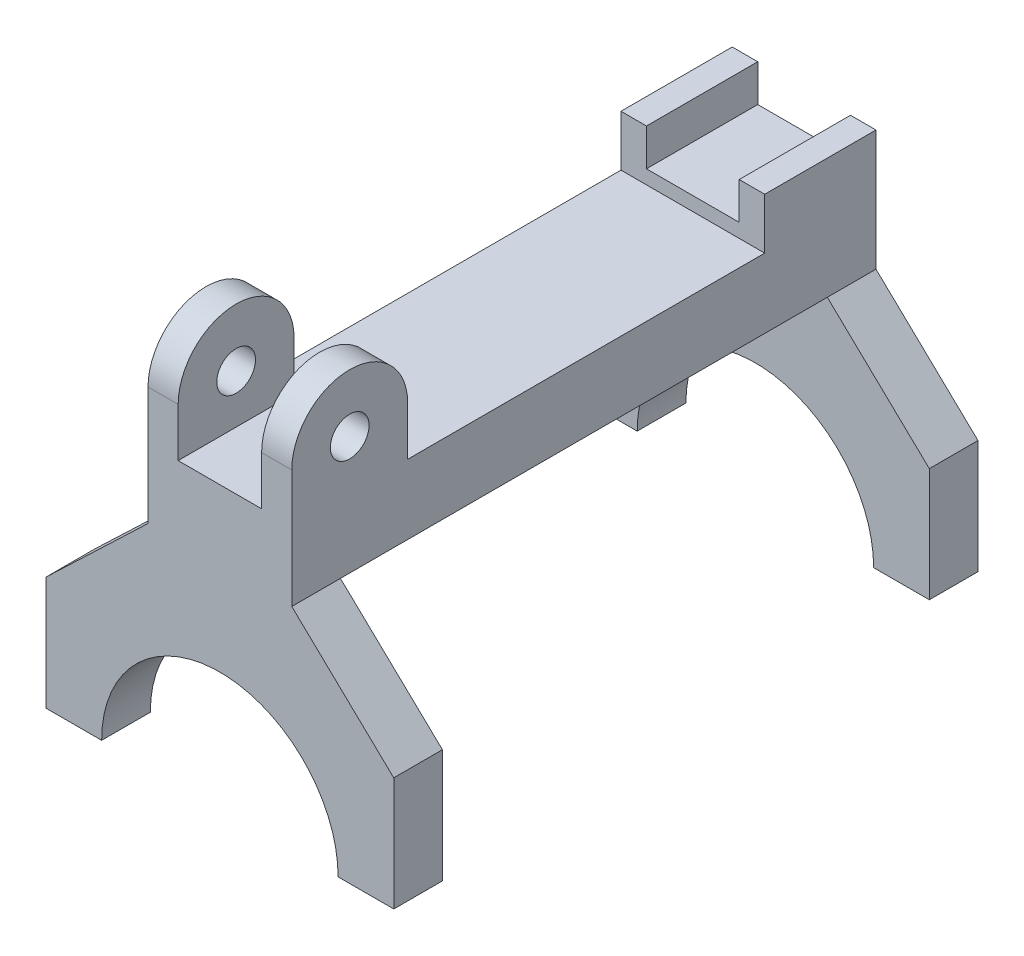
SolidWorks part; units mm, degrees
note: The reader was unsure of these and kept them because the rebuilt part matched: shared geometry of "Sketch1<3>", "Sketch1<4>", "Sketch2<2>".
ref_plane "Front Plane" through (0, 0, 0) normal (0, 0, 1) x (1, 0, 0)
ref_plane "Top Plane" through (0, 0, 0) normal (0, 1, 0) x (1, 0, 0)
ref_plane "Right Plane" through (0, 0, 0) normal (1, 0, 0) x (0, 0, -1)
sketch "Sketch1" plane through (0, 0, 0) normal (1, 0, 0) x (0, 0, -1)
  line L0 (0, 15.24) -> (0, 25.908)
  line L1 (0, 0) -> (128.016, 0)
  line L2 (0, 0) -> (0, 15.24)
  line L3 (25.4, 15.24) -> (0, 15.24)
  line L4 (128.016, 0) -> (128.016, 15.24)
  line L5 (25.4, 15.24) -> (25.4, 25.908)
  line L6 (25.4, 15.24) -> (128.016, 15.24)
  line L7 (128.016, 15.24) -> (103.632, 15.24)
  line L8 (128.016, 15.24) -> (128.016, 26.416)
  line L9 (128.016, 26.416) -> (103.632, 26.416)
  line L10 (103.632, 15.24) -> (103.632, 26.416)
  line L11 (128.016, 15.24) -> (103.632, 15.24)
  line L12 (128.016, 15.24) -> (128.016, 18.288)
  line L13 (128.016, 18.288) -> (103.632, 18.288)
  line L14 (103.632, 15.24) -> (103.632, 18.288)
  arc A0 (25.4, 25.908) -> (0, 25.908) centre (12.7, 25.908) ccw
  circle A1 centre (12.7, 25.908) radius 4.2418
  dimension "D3" = 25.4
  dimension "D6" = 8.4836
  dimension "D1" = 15.24
  dimension "D2" = 128.016
  dimension "D4" = 10.668
  dimension "D5" = 15.24
  dimension "D7" = 11.176
  dimension "D8" = 8.128
  dimension "D9" = 24.384
extrude "Boss-Extrude1" add sketch "Sketch1" along normal blind 10.16 contours L5 A0 L0 L2 L1 L4 L6 A1 | L8 L13 L10 L6
extrude "Boss-Extrude2" add sketch "Sketch1<3>" along direction (1, 0, 0) on the side of the normal offset from surface (1.016 mm away) 9.144 from vertex at 9.144 contours L5 A0 L0 L3 A1 | L6
sketch "Sketch1<3>" plane through (0, 0, 0) normal (1, 0, 0) x (0, 0, -1) same geometry as "Sketch1"
extrude "Boss-Extrude3" add sketch "Sketch1<4>" along normal blind 5.588 from vertex at 10.16 contours L5 A0 L0 L3 A1 | L6 L3 L2 L1 L4 | L13 L8 L9 L10 | L8 L13 L10 L6
sketch "Sketch1<4>" plane through (0, 0, 0) normal (1, 0, 0) x (0, 0, -1) same geometry as "Sketch1"
mirror "Mirror3" about plane through (0, 0, 0) normal (1, 0, 0) of "Boss-Extrude1", "Boss-Extrude2", "Boss-Extrude3"
sketch "Sketch2" plane through (0, 0, 0) normal (0, 0, 1) x (1, 0, 0)
  line L0 (0, 0) -> (0, -46.228) construction
  line L1 (15.748, 0) -> (-15.748, 0) construction
  line L2 (25.908, -46.228) -> (38.1, -46.228)
  line L3 (38.1, -46.228) -> (38.1, -21.336)
  line L4 (38.1, -21.336) -> (15.748, 0)
  line L5 (-15.748, 0) -> (-38.1, -21.336)
  line L6 (-38.1, -21.336) -> (-38.1, -46.228)
  line L7 (-38.1, -46.228) -> (-25.908, -46.228)
  line L16 (9.144, 15.24) -> (-9.144, 15.24)
  line L17 (-9.144, 15.24) -> (-9.144, 25.908)
  line L18 (-9.144, 25.908) -> (-15.748, 25.908)
  line L19 (-15.748, 25.908) -> (-15.748, 0)
  line L20 (-15.748, 0) -> (15.748, 0)
  line L21 (15.748, 0) -> (15.748, 25.908)
  line L22 (15.748, 25.908) -> (9.144, 25.908)
  line L23 (9.144, 25.908) -> (9.144, 15.24)
  line L28 (-15.748, 0) -> (15.748, 0)
  arc A0 (25.908, -46.228) -> (-25.908, -46.228) centre (0, -46.228) ccw
  dimension "D1" = 51.816
  dimension "D2" = 46.228
  dimension "D3" = 24.892
  dimension "D4" = 24.892
  dimension "D5" = 76.2
  dimension "D6" = 0
extrude "Boss-Extrude4" add sketch "Sketch2" against normal blind 10.668
extrude "Boss-Extrude6" add sketch "Sketch2<2>" along normal blind 10.668 from vertex
sketch "Sketch2<2>" plane through (0, 0, 0) normal (0, 0, 1) x (1, 0, 0) same geometry as "Sketch2"
